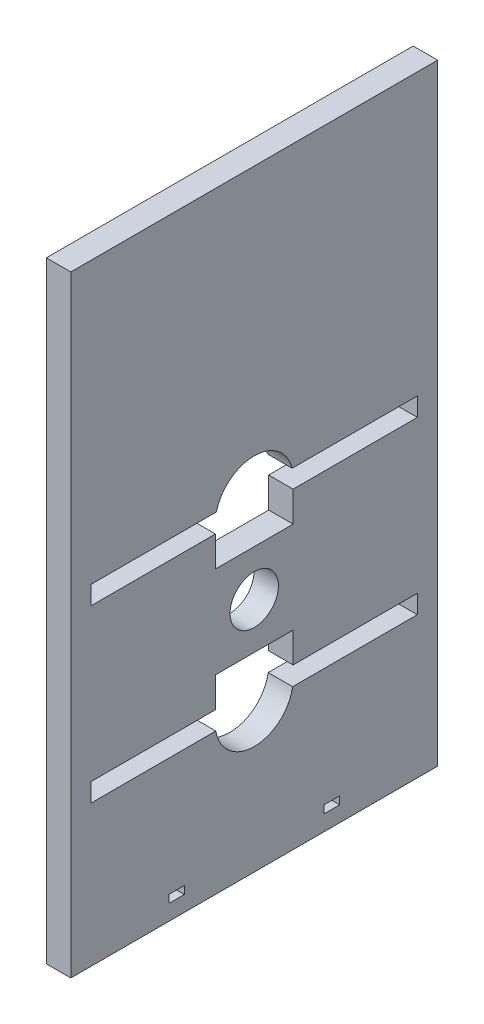
SolidWorks part; units mm, degrees
ref_plane "Front Plane" through (0, 0, 0) normal (0, 0, 1) x (1, 0, 0)
ref_plane "Top Plane" through (0, 0, 0) normal (0, 1, 0) x (1, 0, 0)
ref_plane "Right Plane" through (0, 0, 0) normal (1, 0, 0) x (0, 0, -1)
sketch "Sketch1" plane through (0, 0, 0) normal (1, 0, 0) x (0, 0, -1)
  line L1 (-30, 33.1044) -> (0, 33.1044)
  line L2 (-30, 33.1044) -> (-30, -16.8956)
  line L3 (-30, -16.8956) -> (0, -16.8956)
  line L4 (0, 33.1044) -> (0, -16.8956)
  dimension "D1" = 50
  dimension "D2" = 30
extrude "Boss-Extrude1" add sketch "Sketch1" along normal blind 2
sketch "Sketch2" plane through (2, 0, 0) normal (1, 0, 0) x (0, 0, -1)
  line L0 (-30, -16.8956) -> (0, -16.8956) construction
  line L1 (-21.985, -14.9856) -> (-20.715, -14.9856)
  line L2 (-21.985, -14.9856) -> (-21.985, -15.6256)
  line L3 (-21.985, -15.6256) -> (-20.715, -15.6256)
  line L4 (-20.715, -14.9856) -> (-20.715, -15.6256)
  line L5 (-9.285, -14.9856) -> (-8.015, -14.9856)
  line L6 (-9.285, -14.9856) -> (-9.285, -15.6256)
  line L7 (-9.285, -15.6256) -> (-8.015, -15.6256)
  line L8 (-8.015, -14.9856) -> (-8.015, -15.6256)
  line L9 (-30, 33.1044) -> (-30, -16.8956) construction
  line L10 (-11.9022, 10.1544) -> (-1.66, 10.1544)
  line L11 (-11.8612, -5.3356) -> (-1.665, -5.3356)
  line L12 (-28.335, -3.8156) -> (-18.175, -3.8156)
  line L13 (-28.335, -3.8156) -> (-28.335, -5.3356)
  line L14 (-28.335, -5.3356) -> (-18.1388, -5.3356)
  line L15 (-1.665, -3.8156) -> (-1.665, -5.3356)
  line L16 (-11.825, -3.8156) -> (-1.665, -3.8156)
  line L17 (-18.175, -3.8156) -> (-18.175, -1.3456)
  line L18 (-18.175, -1.3456) -> (-11.825, -1.3456)
  line L19 (-11.825, -1.3456) -> (-11.825, -3.8156)
  line L20 (-28.33, 10.1544) -> (-18.0878, 10.1544)
  line L21 (-28.33, 10.1544) -> (-28.33, 8.6344)
  line L22 (-28.33, 8.6344) -> (-18.17, 8.6344)
  line L23 (-1.66, 10.1544) -> (-1.66, 8.6344)
  line L24 (-11.82, 8.6344) -> (-1.66, 8.6344)
  line L25 (-18.17, 8.6344) -> (-18.17, 6.1544)
  line L26 (-18.17, 6.1544) -> (-11.82, 6.1544)
  line L27 (-11.82, 6.1544) -> (-11.82, 8.6344)
  arc A0 (-18.1388, -5.3356) -> (-11.8612, -5.3356) centre (-15, -4.8256) ccw
  circle A1 centre (-15, 2.4044) radius 1.98
  arc A3 (-11.9022, 10.1544) -> (-18.0878, 10.1544) centre (-14.995, 9.3944) ccw
  point P23 (-15, -1.3456)
  point P37 (-14.995, 6.1544)
  dimension "D13" = 6.36
  dimension "D15" = 3.96
  dimension "D19" = 2.47
  dimension "D1" = 1.27
  dimension "D2" = 1.27
  dimension "D3" = 8.015
  dimension "D4" = 0.64
  dimension "D5" = 1.27
  dimension "D6" = 1.27
  dimension "D7" = 0.64
  dimension "D8" = 11.43
  dimension "D9" = 9.65
  dimension "D10" = 26.67
  dimension "D11" = 1.665
  dimension "D12" = 1.52
  dimension "D14" = 6.35
  dimension "D16" = 3.75
  dimension "D17" = 1.52
  dimension "D18" = 26.67
  dimension "D20" = 2.48
  dimension "D21" = 6.35
  dimension "D22" = 1.67
  dimension "D23" = 7.5
extrude "Cut-Extrude1" cut sketch "Sketch2" against normal blind 2
